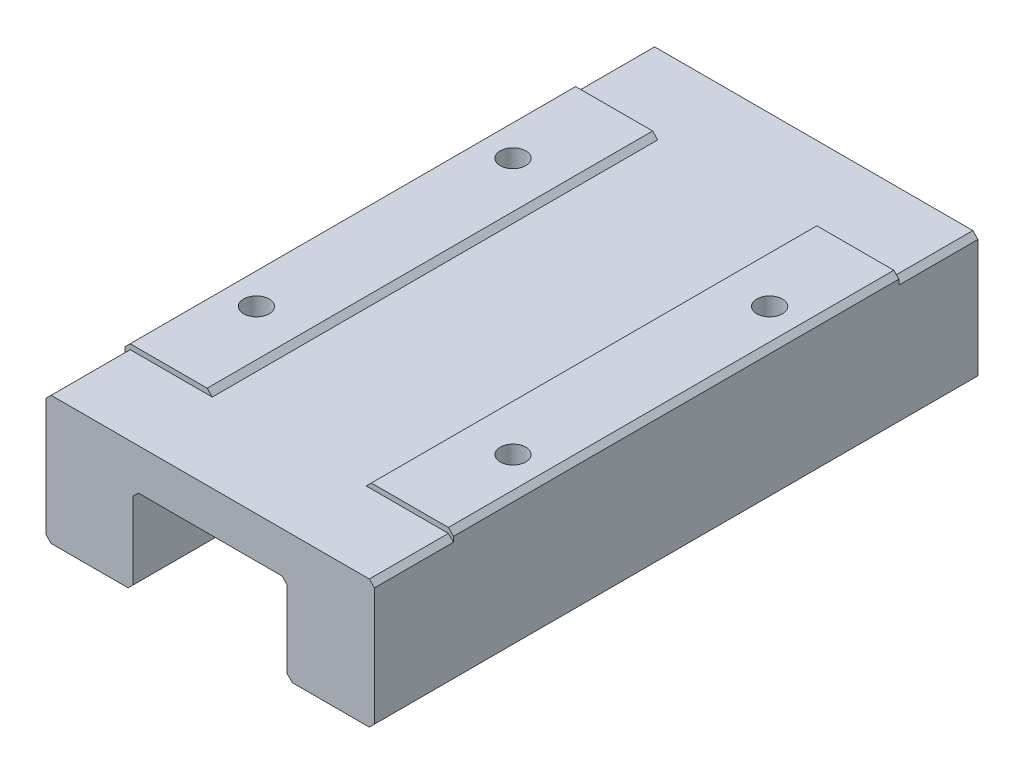
SolidWorks part; units mm, degrees
ref_plane "Front Plane" through (0, 0, 0) normal (0, 0, 1) x (1, 0, 0)
ref_plane "Top Plane" through (0, 0, 0) normal (0, 1, 0) x (1, 0, 0)
ref_plane "Right Plane" through (0, 0, 0) normal (1, 0, 0) x (0, 0, -1)
sketch "Sketch1" plane through (0, 0, 0) normal (0, 1, 0) x (1, 0, 0)
  line L0 (0, 29.4) -> (67.8066, 29.4) construction
  line L1 (0, 0) -> (32, 0)
  line L2 (0, 0) -> (0, 58.8)
  line L3 (0, 58.8) -> (32, 58.8)
  line L4 (32, 0) -> (32, 58.8)
  line L5 (16, -941.2) -> (16, 49058.8) construction
  line L6 (0, 51.1) -> (32, 51.1)
  line L7 (0, 7.7) -> (32, 7.7)
  line L8 (0, 39.4) -> (64.735, 39.4) construction
  line L9 (0, 19.4) -> (70.8781, 19.4) construction
  line L10 (63.6846, 42.8198) -> (72.0744, 15.5053) construction
  point P8 (0, 29.4)
  point P9 (28.5, 17)
  point P11 (16, 58.8)
  point P15 (3.5, 17)
  point P16 (3.5, 42)
  point P17 (28.5, 42)
  dimension "D1" = 32
  dimension "D2" = 58.8
  dimension "D3" = 17
  dimension "D6" = 3.5
  dimension "D7" = 43.4
  dimension "D8" = 7.7
  dimension "D9" = 20
  dimension "D10" = 10
  dimension "D4" = 2
  dimension "D5" = 2
extrude "Boss-Extrude1" add sketch "Sketch1" along normal blind 13 contours L2 L7 L4 L6 | L7 L2 L1 L4 | L2 L6 L4 L3 region at (16, 0, -3.85) region at (16, 0, -29.4) region at (16, 0, -54.95)
hole_wizard "M3x0.5 Tapped Hole1" positions "Sketch2" profile "Sketch3" tap size "M3x0.5" standard "ANSI Metric"
sketch "Sketch2" plane through (0, 13, 0) normal (0, 1, 0) x (1, 0, 0)
  point P0 (28.5, 17)
  point P3 (28.5, 42)
  point P6 (3.5, 42)
  point P9 (3.5, 17)
sketch "Sketch3" plane through (28.5, 13, -17) normal (1, 0, 0) x (0, 0, 1)
  line L0 (0, 0) -> (0, 7.2511)
  line L1 (0, 7.2511) -> (1.25, 6.5)
  line L2 (1.25, 6.5) -> (1.25, 0)
  line L5 (1.25, 0) -> (0, 0)
  line L10 (0, 7.2511) -> (-1.25, 6.5) construction
  line L11 (0, -6.35) -> (0, 107.95) construction
  dimension "Tap Drill Dia." = 2.5
  dimension "Tap Drill Depth" = 6.5
  dimension "Drill Angle" = 118
cosmetic thread "Hole Thread1" parameters "D1"=4, "D2"=3
cosmetic thread "Hole Thread2" parameters "D1"=4, "D2"=3
cosmetic thread "Hole Thread3" parameters "D1"=4, "D2"=3
cosmetic thread "Hole Thread4" parameters "D1"=4, "D2"=3
sketch "Sketch4" plane through (0, 0, 0) normal (0, 0, 1) x (1, 0, 0)
  line L0 (0, 0) -> (32, 0) construction
  line L1 (8.5, 0) -> (23.5, 0)
  line L2 (8.5, 0) -> (8.5, 8.5)
  line L3 (8.5, 8.5) -> (23.5, 8.5)
  line L4 (23.5, 0) -> (23.5, 8.5)
  line L5 (0, 13) -> (0, 0) construction
  line L6 (0, 13) -> (32, 13) construction
  circle A0 centre (16, 10.75) radius 2.25
  point P15 (16, 13)
  point P16 (16, 8.5)
  line M3 (0, 0) -> (32, 0)
  dimension "D3" = 4.5
  dimension "D1" = 8.5
  dimension "D2" = 15
extrude "Cut-Extrude1" cut sketch "Sketch4" against normal through all contours L4 L3 L2 M3 region at (16, 4.25, 0)
sketch "Sketch5" plane through (0, 13, 0) normal (0, 1, 0) x (1, 0, 0)
  line L0 (0, 7.7) -> (32, 7.7) construction
  line L1 (0, 51.1) -> (32, 51.1) construction
  line L2 (0, 7.7) -> (32, 7.7)
  line L3 (0, 51.1) -> (32, 51.1)
  line L4 (16, -200941.2) -> (16, 249058.8) construction
  line L5 (8.5, 51.1) -> (23.5, 51.1)
  line L6 (8.5, 51.1) -> (8.5, 7.7)
  line L7 (8.5, 7.7) -> (23.5, 7.7)
  line L8 (23.5, 51.1) -> (23.5, 7.7)
  circle A1 centre (3.5, 17) radius 1.25
  circle A2 centre (3.5, 17) radius 1.25
  circle A3 centre (3.5, 42) radius 1.25
  circle A4 centre (3.5, 42) radius 1.25
  circle A5 centre (28.5, 42) radius 1.25
  circle A6 centre (28.5, 42) radius 1.25
  circle A7 centre (28.5, 17) radius 1.25
  circle A8 centre (28.5, 17) radius 1.25
  line M11 (0, 58.8) -> (0, 0)
  line M12 (0, 0) -> (32, 0)
  line M13 (32, 0) -> (32, 58.8)
  line M14 (32, 58.8) -> (0, 58.8)
  dimension "D5" = 15
  dimension "D6" = 7.5
  dimension "D1" = 0
  dimension "D2" = 0
  dimension "D3" = 0
  dimension "D4" = 0
extrude "Cut-Extrude2" cut sketch "Sketch5" against normal blind 0.5 contours L3 M11 M13 M14 | L2 M11 M12 M13 | L8 L3 L6 L2 region at (16, 13, -3.85) region at (16, 13, -29.4) region at (16, 13, -54.95)
chamfer "Chamfer1" distance 0.5 angle 45 14 edges at (32, 0, -29.4) (23.5, 0, -29.4) (8.5, 0, -29.4) (0, 0, -29.4) (0, 12.5, -54.95) (32, 12.5, -54.95) (32, 12.5, -3.85) (0, 12.5, -3.85) (0, 13, -29.4) (32, 13, -29.4) (23.5, 13, -29.4) (8.5, 13, -29.4) (8.5, 8.5, -29.4) (23.5, 8.5, -29.4)
